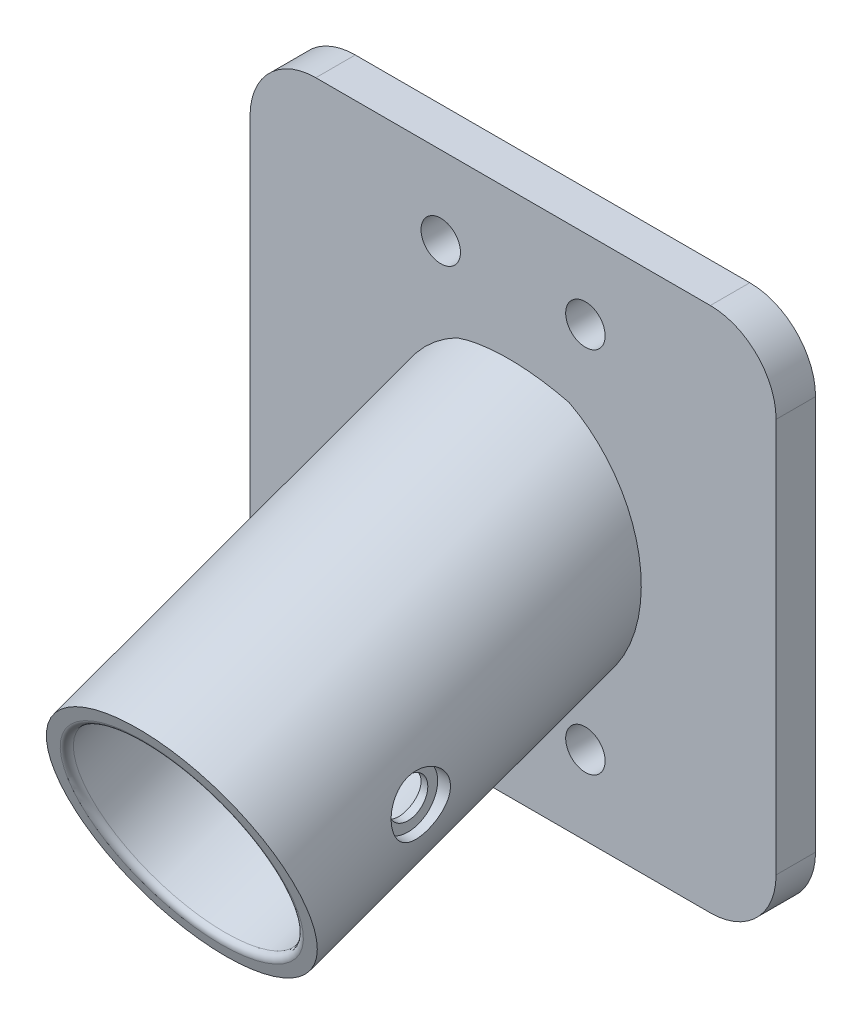
SolidWorks part; units mm, degrees
ref_plane "前基準面" through (0, 0, 0) normal (0, 0, 1) x (1, 0, 0)
ref_plane "上基準面" through (0, 0, 0) normal (0, 1, 0) x (1, 0, 0)
ref_plane "右基準面" through (0, 0, 0) normal (1, 0, 0) x (0, 0, -1)
sketch "草圖1" plane through (0, 0, 0) normal (0, 0, 1) x (1, 0, 0)
  line L1 (-15, 20) -> (15, 20)
  line L2 (-20, 15) -> (-20, -15)
  line L3 (-15, -20) -> (15, -20)
  line L4 (20, 15) -> (20, -15)
  line L5 (-20, 20) -> (20, -20) construction
  line L6 (-20, -20) -> (20, 20) construction
  arc A0 (15, -20) -> (20, -15) centre (15, -15) ccw
  arc A1 (-20, -15) -> (-15, -20) centre (-15, -15) ccw
  arc A2 (15, 20) -> (20, 15) centre (15, 15) cw
  arc A3 (-15, 20) -> (-20, 15) centre (-15, 15) ccw
  point P0 (0, 0)
  dimension "D2" = 5
  dimension "D1" = 40
extrude "填料-伸長1" add sketch "草圖1" along normal blind 3
ref_axis "基準軸1" through (-22, 0, 0) along (1, 0, 0)
ref_plane "平面1" through (0, 0, 0) normal (0, -0.342, 0.9397) x (1, 0, 0)
sketch "草圖2" plane through (0, 0, 0) normal (0, 0, 1) x (1, 0, 0)
  line L0 (-1000, 0) -> (49000, 0) construction
  line L1 (0, -1000) -> (0, 49000) construction
  line L2 (-1013.5593, 14) -> (48986.4407, 14)
  line L3 (-1013.5593, -14) -> (48986.4407, -14)
  line L4 (-5.5, -984.1658) -> (-5.5, 49015.8342)
  line L5 (5.5, -984.1658) -> (5.5, 49015.8342)
  line L6 (15, 20) -> (-15, 20) construction
  line L7 (-15, -20) -> (15, -20) construction
  circle A0 centre (-5.5, 14) radius 1.5
  circle A1 centre (5.5, 14) radius 1.5
  circle A2 centre (5.5, -14) radius 1.5
  circle A3 centre (-5.5, -14) radius 1.5
  dimension "D1" = 3
  dimension "D2" = 6
  dimension "D3" = 6
  dimension "D4" = 11
extrude "除料-伸長2" cut sketch "草圖2" against normal through all and the other way through all
sketch "草圖3" plane through (0, 0, 0) normal (0, -0.342, 0.9397) x (1, 0, 0)
  circle A0 centre (0, 0) radius 9.75
  circle A1 centre (0, 0) radius 8.25
  dimension "D1" = 16.5
  dimension "D2" = 19.5
extrude "填料-伸長2" add sketch "草圖3" along normal blind 30
sketch "草圖4" plane through (0, 0, 0) normal (1, 0, 0) x (0, 0, -1)
  line L1 (0, 20) -> (10.0939, 20)
  line L2 (0, 20) -> (0, -19.9792)
  line L3 (0, -19.9792) -> (10.0939, -19.9792)
  line L4 (10.0939, 20) -> (10.0939, -19.9792)
extrude "除料-伸長3" cut sketch "草圖4" against normal mid plane 25
sketch "草圖5" plane through (0, 0, 0) normal (1, 0, 0) x (0, 0, -1)
  line L0 (-23.4923, -8.5505) -> (46961.1387, 17092.4567) construction
  line L1 (-31.5255, -1.0986) -> (-24.8561, -19.4226) construction
  circle A0 centre (-19.7335, -7.1824) radius 1.5
  point P4 (-28.1908, -10.2606)
  dimension "D2" = 3
  dimension "D1" = 21
extrude "除料-伸長4" cut sketch "草圖5" against normal through all both and the other way through all
ref_plane "平面2" through (9.75, 0, 0) normal (1, 0, 0) x (0, 0, -1)
sketch "草圖6" plane through (9.75, 0, 0) normal (1, 0, 0) x (0, 0, -1)
  circle A0 centre (-19.7335, -7.1824) radius 2.25
  dimension "D1" = 4.5
extrude "除料-伸長5" cut sketch "草圖6" against normal blind 1
ref_plane "平面3" through (-9.75, 0, 0) normal (1, 0, 0) x (0, 0, -1)
sketch "草圖7" plane through (-9.75, 0, 0) normal (1, 0, 0) x (0, 0, -1)
  line L0 (-24.8561, -19.4226) -> (-3, -11.4676) construction
  line L1 (-17.301, -9.2235) -> (-16.7496, -6.0964)
  line L2 (-16.7496, -6.0964) -> (-19.1821, -4.0552)
  line L3 (-19.1821, -4.0552) -> (-22.1661, -5.1413)
  line L4 (-22.1661, -5.1413) -> (-22.7175, -8.2685)
  line L5 (-22.7175, -8.2685) -> (-20.285, -10.3096)
  line L6 (-20.285, -10.3096) -> (-17.301, -9.2235)
  circle A0 centre (-19.7335, -7.1824) radius 2.75 construction
  dimension "D1" = 5.5
extrude "除料-伸長6" cut sketch "草圖7" along normal blind 1
fillet "圓角1" radius 0.5 1 edges at (0, -18.0131, 25.3691)
